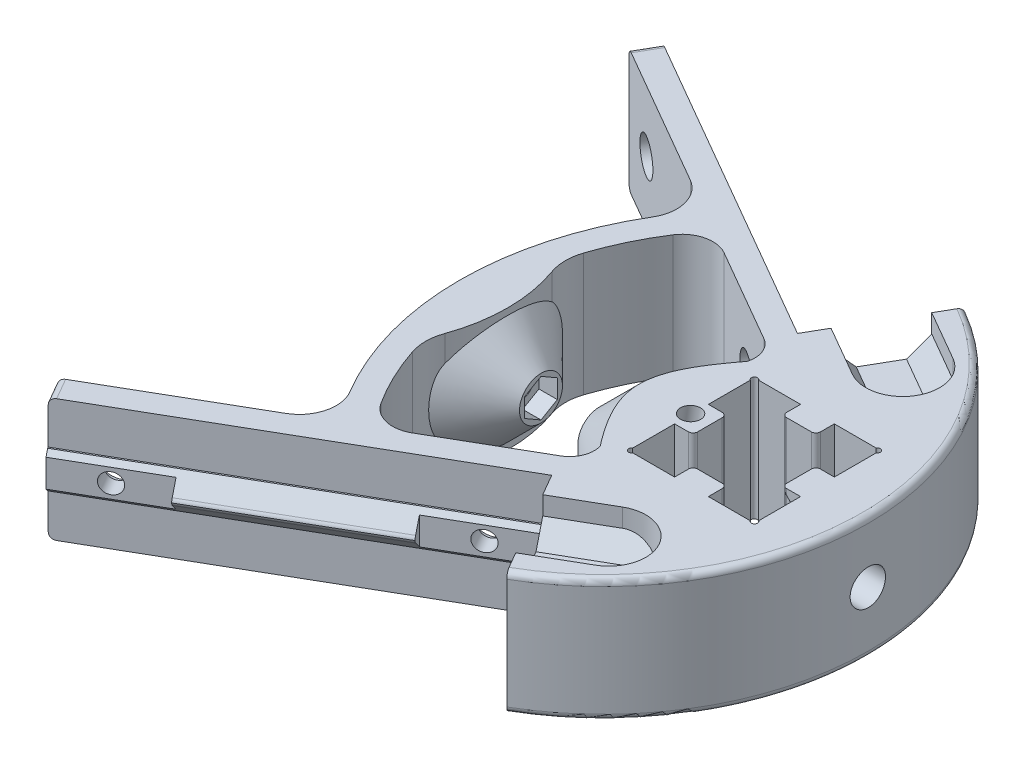
SolidWorks part; units mm, degrees
ref_plane "Front Plane" through (0, 0, 0) normal (0, 0, 1) x (1, 0, 0)
ref_plane "Top Plane" through (0, 0, 0) normal (0, 1, 0) x (1, 0, 0)
ref_plane "Right Plane" through (0, 0, 0) normal (1, 0, 0) x (0, 0, -1)
sketch "Sketch-extrusion profile" plane through (0, 0, 0) normal (0, 1, 0) x (1, 0, 0)
  line L0 (0, 7) -> (0, 0) construction
  line L1 (0, 7) -> (-2, 7) construction
  line L2 (-3, 8) -> (-3, 10) construction
  line L3 (-3, 10) -> (-10, 10) construction
  line L4 (0, 0) -> (-10, 10) construction
  line L5 (-7, 0) -> (-7, 2) construction
  line L6 (-8, 3) -> (-10, 3) construction
  line L7 (-10, 3) -> (-10, 10) construction
  line L8 (7, 0) -> (7, 2) construction
  line L9 (8, 3) -> (10, 3) construction
  line L10 (10, 3) -> (10, 10) construction
  line L11 (3, 10) -> (10, 10) construction
  line L12 (3, 8) -> (3, 10) construction
  line L13 (0, 7) -> (2, 7) construction
  line L14 (0, -7) -> (2, -7) construction
  line L15 (3, -8) -> (3, -10) construction
  line L16 (3, -10) -> (10, -10) construction
  line L17 (10, -3) -> (10, -10) construction
  line L18 (8, -3) -> (10, -3) construction
  line L19 (7, 0) -> (7, -2) construction
  line L20 (-7, 0) -> (-7, -2) construction
  line L21 (-8, -3) -> (-10, -3) construction
  line L22 (-10, -3) -> (-10, -10) construction
  line L23 (-3, -10) -> (-10, -10) construction
  line L24 (-3, -8) -> (-3, -10) construction
  line L25 (0, -7) -> (-2, -7) construction
  line L26 (0, 0) -> (4.0502, 0) construction
  line L27 (10.25, 2.75) -> (10.25, 9.567)
  line L28 (2.75, 10.25) -> (9.567, 10.25)
  line L29 (2.75, 8) -> (2.75, 10.25)
  line L30 (0, 7.25) -> (2, 7.25)
  line L31 (0, 7.25) -> (-2, 7.25)
  line L32 (-2.75, 8) -> (-2.75, 10.25)
  line L33 (-2.75, 10.25) -> (-9.567, 10.25)
  line L34 (-10.25, 2.75) -> (-10.25, 9.567)
  line L35 (-8, 2.75) -> (-10.25, 2.75)
  line L36 (-7.25, 0) -> (-7.25, 2)
  line L37 (-7.25, 0) -> (-7.25, -2)
  line L38 (-8, -2.75) -> (-10.25, -2.75)
  line L39 (-10.25, -2.75) -> (-10.25, -9.567)
  line L40 (-2.75, -10.25) -> (-9.567, -10.25)
  line L41 (-2.75, -8) -> (-2.75, -10.25)
  line L42 (0, -7.25) -> (-2, -7.25)
  line L43 (0, -7.25) -> (2, -7.25)
  line L44 (2.75, -8) -> (2.75, -10.25)
  line L45 (2.75, -10.25) -> (9.567, -10.25)
  line L46 (10.25, -2.75) -> (10.25, -9.567)
  line L47 (8, -2.75) -> (10.25, -2.75)
  line L48 (7.25, 0) -> (7.25, -2)
  line L49 (7.25, 0) -> (7.25, 2)
  line L50 (8, 2.75) -> (10.25, 2.75)
  line L51 (-10.25, 2.75) -> (-10.25, 10.25) construction
  line L52 (-2.75, 10.25) -> (-10.25, 10.25) construction
  line L53 (-10.25, -2.75) -> (-10.25, -10.25) construction
  line L54 (-2.75, -10.25) -> (-10.25, -10.25) construction
  line L55 (2.75, -10.25) -> (10.25, -10.25) construction
  line L56 (10.25, -2.75) -> (10.25, -10.25) construction
  line L57 (2.75, 10.25) -> (10.25, 10.25) construction
  line L58 (10.25, 2.75) -> (10.25, 10.25) construction
  arc A0 (-7, 2) -> (-8, 3) centre (-8, 2) ccw construction
  arc A1 (-7, -2) -> (-8, -3) centre (-8, -2) cw construction
  arc A2 (-3, -8) -> (-2, -7) centre (-2, -8) cw construction
  arc A3 (2, -7) -> (3, -8) centre (2, -8) cw construction
  arc A4 (8, -3) -> (7, -2) centre (8, -2) cw construction
  arc A5 (7, 2) -> (8, 3) centre (8, 2) cw construction
  arc A6 (3, 8) -> (2, 7) centre (2, 8) cw construction
  arc A7 (-2, 7) -> (-3, 8) centre (-2, 8) cw construction
  arc A8 (2.75, 8) -> (2, 7.25) centre (2, 8) cw
  arc A9 (-2, 7.25) -> (-2.75, 8) centre (-2, 8) cw
  arc A10 (-7.25, 2) -> (-8, 2.75) centre (-8, 2) ccw
  arc A11 (-7.25, -2) -> (-8, -2.75) centre (-8, -2) cw
  arc A12 (-2.75, -8) -> (-2, -7.25) centre (-2, -8) cw
  arc A13 (2, -7.25) -> (2.75, -8) centre (2, -8) cw
  arc A14 (8, -2.75) -> (7.25, -2) centre (8, -2) cw
  arc A15 (7.25, 2) -> (8, 2.75) centre (8, 2) cw
  arc A16 (-10.25, 9.567) -> (-9.567, 10.25) centre (-10, 10) cw
  arc A17 (-10.25, -9.567) -> (-9.567, -10.25) centre (-10, -10) ccw
  arc A18 (9.567, -10.25) -> (10.25, -9.567) centre (10, -10) ccw
  arc A19 (9.567, 10.25) -> (10.25, 9.567) centre (10, 10) cw
  point P10 (-7, 3)
  point P31 (0, 0)
  point P44 (-3, 7)
  dimension "D6" = 1
  dimension "D7" = 0.25
  dimension "D8" = 0.5
  dimension "D1" = 7
  dimension "D2" = 7
  dimension "D3" = 3
  dimension "D4" = 3
  dimension "D5" = 4
sketch "Sketch-main" plane through (0, 0, 0) normal (0, 1, 0) x (1, 0, 0)
  line L0 (-7, 0) -> (7, 0) construction
  line L1 (0, 7) -> (0, -7) construction
  line L2 (-13, 20) -> (-64.9615, 50)
  line L3 (-13, 20) -> (-3, 37.3205)
  line L4 (-64.9615, 50) -> (-66.9615, 46.5359)
  line L6 (-13, 20) -> (-24.547, 0) construction
  line L8 (3.9461, 0) -> (-11.0539, 0) construction
  line L9 (-11.0539, -14.2576) -> (-11.0539, 14.2576) construction
  line L14 (-13, -20) -> (-3, -37.3205)
  line L15 (-13, -20) -> (-64.9615, -50)
  line L16 (-64.9615, -50) -> (-66.9615, -46.5359)
  line L30 (-66.9615, 46.5359) -> (-15.004, 16.5382)
  line L31 (-66.9615, -46.5359) -> (-15.004, -16.5382)
  arc A0 (-3, 37.3205) -> (-3, -37.3205) centre (-24.547, 0) cw
  arc A1 (-13.6106, 10.9564) -> (-13.6106, -10.9564) centre (3.9461, 0) ccw
  arc A2 (-13.6106, -10.9564) -> (-15.004, -16.5382) centre (-17.004, -13.0741) cw
  arc A3 (-15.004, 16.5382) -> (-13.6106, 10.9564) centre (-17.004, 13.0741) cw
  dimension "D7" = 15
  dimension "D8" = 4
  dimension "D1" = 20
  dimension "D2" = 13
  dimension "D3" = 20
  dimension "D4" = 30
  dimension "D5" = 60
  dimension "D6" = 4
extrude "Boss-Extrude1" add sketch "Sketch-main" along normal blind 10 and the other way blind 10
extrude "Cut-Extrude1" cut sketch "Sketch-extrusion profile" against normal through all both and the other way through all
sketch "Sketch1" plane through (-18.4103, 0, -10.6292) normal (-0.866, 0, -0.5) x (-0.5, 0, 0.866)
  line L0 (-30.8205, 0) -> (-10.8205, 0) construction
  line L1 (-30.8205, -10) -> (-30.8205, 10) construction
  line L2 (-10.8205, -10) -> (-10.8205, 10) construction
  line L3 (-20.8205, 10) -> (-20.8205, 0) construction
  line L4 (-30.8205, 10) -> (-10.8205, 10) construction
  line L5 (-17.8205, 4) -> (-23.8205, 4)
  line L6 (-23.8205, 4) -> (-26.8205, 7)
  line L7 (-26.8205, 7) -> (-26.8205, 10)
  line L8 (-26.8205, 10) -> (-14.8205, 10)
  line L9 (-17.8205, 4) -> (-14.8205, 7)
  line L10 (-14.8205, 7) -> (-14.8205, 10)
  line L11 (-23.8205, -4) -> (-26.8205, -7)
  line L12 (-17.8205, -4) -> (-23.8205, -4)
  line L13 (-17.8205, -4) -> (-14.8205, -7)
  line L14 (-14.8205, -7) -> (-14.8205, -10)
  line L15 (-26.8205, -10) -> (-14.8205, -10)
  line L16 (-26.8205, -7) -> (-26.8205, -10)
  point P15 (-20.8205, 4)
  dimension "D1" = 6
  dimension "D2" = 3
  dimension "D3" = 6
  dimension "D4" = 12
extrude "Cut-Extrude2" cut sketch "Sketch1" against normal blind 15.5
mirror "Mirror1" about plane through (0, 0, 0) normal (0, 0, 1) of "Cut-Extrude2"
fillet "Fillet1" radius 6 8 edges at (2.4234, -8.5, 15.7141) (8.4234, -8.5, 26.1064) (2.4234, 8.5, 15.7141) (8.4234, 8.5, 26.1064) (2.4234, -8.5, -15.7141) (8.4234, -8.5, -26.1064) (8.4234, 8.5, -26.1064) (2.4234, 8.5, -15.7141)
sketch "Sketch3" plane through (5.4103, 0, -9.3708) normal (0.5, 0, -0.866) x (-0.866, 0, -0.5)
  line L0 (21.2583, 0) -> (81.2583, 0) construction
  line L1 (21.2583, -10) -> (21.2583, 10) construction
  line L2 (81.2583, -10) -> (81.2583, 10) construction
  line L3 (21.2583, -10) -> (81.2583, -10) construction
  line L5 (21.2583, -3) -> (81.2583, -3)
  line L6 (21.2583, -3) -> (21.2583, 3)
  line L7 (21.2583, 3) -> (81.2583, 3)
  line L8 (81.2583, -3) -> (81.2583, 3)
  line L9 (21.2583, -3) -> (81.2583, 3) construction
  line L10 (21.2583, 3) -> (81.2583, -3) construction
  point P8 (51.2583, 0)
  dimension "D1" = 10
  dimension "D2" = 6
extrude "Boss-Extrude2" add sketch "Sketch3" along normal blind 3
sketch "Sketch7" plane through (6.9103, 0, -11.9689) normal (0.5, 0, -0.866) x (-0.866, 0, -0.5)
  line L0 (51.2583, 3) -> (51.2583, -3) construction
  line L1 (81.2583, 3) -> (21.2583, 3) construction
  line L2 (21.2583, -3) -> (81.2583, -3) construction
  line L3 (21.2583, -3) -> (81.2583, -3) construction
  line L4 (21.2583, 3) -> (36.7583, 3)
  line L5 (21.2583, 3) -> (21.2583, -3)
  line L6 (21.2583, -3) -> (36.7583, -3)
  line L7 (36.7583, 3) -> (36.7583, -3)
  line L8 (81.2583, -3) -> (65.7583, -3)
  line L9 (65.7583, 3) -> (65.7583, -3)
  line L10 (81.2583, 3) -> (65.7583, 3)
  line L11 (81.2583, 3) -> (81.2583, -3)
  dimension "D1" = 15.5
extrude "Cut-Extrude6" cut sketch "Sketch7" against normal blind 2
sketch "Sketch34" plane through (-70.3718, 0, -40.6292) normal (-0.866, 0, -0.5) x (-0.5, 0, 0.866)
  line L0 (-11.0705, 3) -> (-13.8205, 0.25)
  line L1 (-11.8205, 3) -> (-10.8205, 3) construction
  line L2 (-13.8205, 3) -> (-13.8205, -3) construction
  line L3 (-10.8205, 3) -> (-10.8205, 10) construction
  line L4 (-11.8205, 0) -> (-13.8205, 0) construction
  line L5 (-11.8205, -3) -> (-11.8205, 3) construction
  line L6 (-13.8205, 0.25) -> (-13.8205, 3)
  line L7 (-13.8205, 3) -> (-11.0705, 3)
  line L9 (-13.8205, -3) -> (-11.0705, -3)
  line L10 (-13.8205, -0.25) -> (-13.8205, -3)
  line L11 (-11.0705, -3) -> (-13.8205, -0.25)
  dimension "D1" = 0.25
  dimension "D2" = 45
extrude "Cut-Extrude25" cut sketch "Sketch34" against normal blind 60
sketch "Sketch8" plane through (3.4103, 0, -5.9067) normal (-0.5, 0, 0.866) x (0.866, 0, 0.5)
  line L0 (-73.5083, 3) -> (-73.5083, -3) construction
  line L1 (-81.2583, 3) -> (-65.7583, 3) construction
  line L2 (-81.2583, -3) -> (-65.7583, -3) construction
  line L3 (-51.2583, 0) -> (-51.2583, 10) construction
  line L4 (-51.2583, 3) -> (-51.2583, -3) construction
  line L5 (-81.2583, 10) -> (-21.263, 10) construction
  circle A0 centre (-73.5083, 0) radius 1.625
  circle A1 centre (-29.0083, 0) radius 1.625
  dimension "D1" = 3.25
extrude "Cut-Extrude7" cut sketch "Sketch8" against normal through all
sketch "Sketch9" plane through (3.4103, 0, -5.9067) normal (-0.5, 0, 0.866) x (0.866, 0, 0.5)
  circle A0 centre (-73.5083, 0) radius 2.875
  circle A1 centre (-29.0083, 0) radius 2.875
  dimension "D1" = 5.75
extrude "Cut-Extrude8" cut sketch "Sketch9" against normal blind 2
fillet "Fillet3" radius 1 2 edges at (-37.4808, -0.25, -37.5981) (-37.4808, 0.25, -37.5981)
mirror "Mirror4" about plane through (0, 0, 0) normal (0, 0, 1) of "Fillet3", "Cut-Extrude25", "Cut-Extrude8", "Cut-Extrude7", "Cut-Extrude6", "Boss-Extrude2"
sketch "Sketch10" plane through (7.25, 0, 0) normal (-1, 0, 0) x (0, 0, 1)
  line L0 (0, 10) -> (0, -10) construction
  line L1 (2, 10) -> (-2, 10) construction
  line L2 (2, -10) -> (-2, -10) construction
  circle A0 centre (0, 0) radius 1.625
  dimension "D2" = 3.25
  dimension "D1" = 10
extrude "Cut-Extrude9" cut sketch "Sketch10" against normal through all
sketch "Sketch11" plane through (7.25, 0, 0) normal (-1, 0, 0) x (0, 0, 1)
  line L0 (-2.75, -10) -> (-2.75, 10) construction
  line L1 (2.75, -7.75) -> (-2.75, -7.75)
  line L2 (2.75, -7.75) -> (2.75, 7.75)
  line L3 (2.75, 7.75) -> (-2.75, 7.75)
  line L4 (-2.75, -7.75) -> (-2.75, 7.75)
  line L5 (2.75, -7.75) -> (-2.75, 7.75) construction
  line L6 (2.75, 7.75) -> (-2.75, -7.75) construction
  point P0 (0, 0)
  dimension "D1" = 15.5
extrude "Cut-Extrude11" cut sketch "Sketch11" against normal blind 2
ref_plane "Plane1" through (18.547, 10, 0) normal (1, 0, 0) x (0, 0, -1)
sketch "Sketch13" plane through (18.547, 10, 0) normal (1, 0, 0) x (0, 0, -1)
  circle A0 centre (0, -10) radius 2.875
  dimension "D1" = 5.75
extrude "Cut-Extrude12" cut sketch "Sketch13" against normal offset from surface (6.297 mm away) 2 up to face at (10.25, 0, 6.1585)
sketch "Sketch27" plane through (0, 0, 2.75) normal (0, 0, 1) x (1, 0, 0)
  line L0 (9.25, 7.75) -> (8, 7.75) construction
  line L1 (7.25, 7.75) -> (8, 7.75) construction
  line L2 (9.25, -7.75) -> (8, -7.75) construction
  line L3 (8, -7.75) -> (7.25, -7.75) construction
  line L4 (9.25, 7.75) -> (8, 7.75)
  line L5 (7.25, 7.75) -> (8, 7.75)
  line L6 (9.25, -7.75) -> (8, -7.75)
  line L7 (8, -7.75) -> (7.25, -7.75)
  line L8 (7.25, -7.75) -> (7.25, -9.75)
  line L9 (7.25, -9.75) -> (9.25, -7.75)
  line L10 (7.25, 7.75) -> (7.25, 9.75)
  line L11 (7.25, 9.75) -> (9.25, 7.75)
  dimension "D1" = 45
  dimension "D2" = 45
extrude "Cut-Extrude19" cut sketch "Sketch27" against normal up to next
mirror "Mirror5" [suppressed] about plane through (0, 0, 0) normal (0, 1, 0)
fillet "Fillet8" radius 1 6 edges at (18.547, -10, 0) (18.547, 10, 0) (-65.9615, -10, 48.2679) (-65.9615, 10, 48.2679) (-65.9615, -10, -48.2679) (-65.9615, 10, -48.2679)
sketch "Sketch14" [suppressed] plane through (0, 0, 0) normal (0, 1, 0) x (1, 0, 0)
  line L0 (-11.75, 22.1651) -> (-2.75, 16.9689)
  line L1 (-2.75, 16.9689) -> (-2.75, 7.25)
  line L2 (-2.75, 8) -> (-2.75, 10.25) construction
  line L3 (2, 7.25) -> (-2, 7.25) construction
  line L4 (2.75, 10.25) -> (2.75, 8) construction
  line L5 (3.2272, 29.1064) -> (-5, 33.8564) construction
  line L6 (-11.75, 22.1651) -> (-4.25, 35.1554)
  line L7 (-11, 23.4641) -> (-13, 20) construction
  line L8 (-3.5, 36.4545) -> (-5, 33.8564) construction
  line L9 (-4.25, 35.1554) -> (2.75, 31.114)
  line L10 (2.75, 31.114) -> (2.75, 7.25)
  line L11 (2.75, 7.25) -> (-2.75, 7.25)
  line L12 (-2.7728, 18.7141) -> (-11, 23.4641) construction
  line L13 (0, 0) -> (-39.9382, 0) construction
  line L14 (-2.75, -16.9689) -> (-2.75, -7.25)
  line L15 (2.75, -7.25) -> (-2.75, -7.25)
  line L16 (2.75, -31.114) -> (2.75, -7.25)
  line L17 (-4.25, -35.1554) -> (2.75, -31.114)
  line L18 (-11.75, -22.1651) -> (-2.75, -16.9689)
  line L19 (-11.75, -22.1651) -> (-4.25, -35.1554)
  dimension "D1" = 1.5
  dimension "D2" = 1.5
extrude "Cut-Extrude13" [suppressed] cut sketch "Sketch14" against normal offset from surface 4 and the other way offset from surface 4 up to face at (-0.156, -4, -24.1315) other way up to face at (-0.156, 4, -24.1315)
sketch "Sketch28" [suppressed] plane through (2.75, 0, 0) normal (1, 0, 0) x (0, 0, -1)
  line L0 (7.25, 10) -> (10.25, 10)
  line L1 (7.25, 10) -> (8, 10) construction
  line L2 (10.25, 10) -> (8, 10) construction
  line L3 (10.25, -20) -> (10.25, 20) construction
  line L4 (10.25, 10) -> (7.25, 13)
  line L5 (7.25, 10) -> (7.25, 20) construction
  line L6 (7.25, 13) -> (7.25, 10)
  line L7 (5.3832, 0) -> (-4.7577, 0) construction
  line L8 (0, 2.994) -> (0, -3.4826) construction
  line L9 (-7.25, 10) -> (-10.25, 10)
  line L10 (-10.25, 10) -> (-7.25, 13)
  line L11 (-7.25, 13) -> (-7.25, 10)
  line L12 (7.25, -10) -> (10.25, -10)
  line L13 (10.25, -10) -> (7.25, -13)
  line L14 (7.25, -13) -> (7.25, -10)
  line L15 (-7.25, -13) -> (-7.25, -10)
  line L16 (-7.25, -10) -> (-10.25, -10)
  line L17 (-10.25, -10) -> (-7.25, -13)
  dimension "D1" = 45
extrude "Cut-Extrude20" [suppressed] cut sketch "Sketch28" against normal up to next
fillet "Fillet6" [suppressed] radius 5
sketch "Sketch18" [suppressed] plane through (18.547, 20, 0) normal (1, 0, 0) x (0, 0, -1)
  line L0 (-37.3205, -22.142) -> (37.3205, -22.142) construction
  line L1 (-37.3205, -39) -> (-37.3205, -1) construction
  line L2 (37.3205, -39) -> (37.3205, -1) construction
  line L3 (40.0914, -28.3306) -> (-3.7181, -28.3306) construction
  text T0 "KosseL" font "Jefferies" height 8
  text T1 "minimax" font "Trebuchet MS" height 4.5
wrap "Wrap1" [suppressed] sketch "Sketch18" source sketch "Sketch18" thickness 0.25 parameters "D1"=0.25
sketch "Sketch29" [suppressed] plane through (0, 0, 0) normal (0, 1, 0) x (1, 0, 0)
  line L0 (-45, 25.1962) -> (-45, -25.1962)
  line L1 (-66.0955, 46.0359) -> (-15.004, 16.5382) construction
  line L2 (-15.004, -16.5382) -> (-66.0955, -46.0359) construction
  line L3 (-49, 27.5056) -> (-49, -27.5056)
  line L4 (0, 5.0299) -> (0, -2.8868) construction
  line L5 (-3.4206, 0) -> (3.3651, 0) construction
  line L6 (-56.5, 40.4959) -> (-53.5973, 38.8201)
  line L7 (-53.5973, 38.8201) -> (-51.5973, 42.2842)
  line L8 (-13, 20) -> (-64.0955, 49.5) construction
  line L9 (-51.5973, 42.2842) -> (-26.4641, 27.7735)
  line L11 (-26.4641, 27.7735) -> (-28.4641, 24.3094)
  line L12 (-28.4641, 24.3094) -> (-37.5, 29.5263)
  line L13 (-28.4641, -24.3094) -> (-37.5, -29.5263)
  line L14 (-26.4641, -27.7735) -> (-28.4641, -24.3094)
  line L15 (-51.5973, -42.2842) -> (-26.4641, -27.7735)
  line L16 (-53.5973, -38.8201) -> (-51.5973, -42.2842)
  line L17 (-56.5, -40.4959) -> (-53.5973, -38.8201)
  arc A0 (-45, -25.1962) -> (-37.5, -29.5263) centre (-40, -25.1962) ccw
  arc A1 (-45, 25.1962) -> (-37.5, 29.5263) centre (-40, 25.1962) cw
  arc A2 (-49, -27.5056) -> (-56.5, -40.4959) centre (-64, -27.5056) cw
  arc A3 (-49, 27.5056) -> (-56.5, 40.4959) centre (-64, 27.5056) ccw
  point P27 (-45, -33.8564)
  point P30 (-45, 33.8564)
  point P33 (-49, -36.1658)
  point P36 (-49, 36.1658)
  dimension "D3" = 5
  dimension "D4" = 15
  dimension "D1" = 4
  dimension "D2" = 45
extrude "Boss-Extrude6" [suppressed] add sketch "Sketch29" along normal up to surface and the other way up to surface up to face at (0, 10, 0) other way up to face at (0, -10, 0)
sketch "Sketch30" [suppressed] plane through (-45, 0, 0) normal (1, 0, 0) x (0, 0, -1)
  line L0 (0, 20) -> (0, -20) construction
  line L1 (25.1962, 20) -> (-25.1962, 20) construction
  line L2 (-25.1962, -20) -> (25.1962, -20) construction
  line L3 (0, 0) -> (9.6965, 0) construction
  circle A0 centre (0, 0) radius 15
  circle A1 centre (-15.495, 15.495) radius 1.625
  circle A2 centre (15.495, 15.495) radius 1.625
  circle A3 centre (15.495, -15.495) radius 1.625
  circle A4 centre (-15.495, -15.495) radius 1.625
  dimension "D1" = 30
  dimension "D2" = 3.25
  dimension "D3" = 30.99
  dimension "D4" = 30.99
extrude "Cut-Extrude21" [suppressed] cut sketch "Sketch30" against normal up to next
sketch "Sketch31" [suppressed] plane through (-45, 0, 0) normal (1, 0, 0) x (0, 0, -1)
  circle A0 centre (-15.495, 15.495) radius 2.875
  circle A1 centre (15.495, 15.495) radius 2.875
  circle A2 centre (15.495, -15.495) radius 2.875
  circle A3 centre (-15.495, -15.495) radius 2.875
  dimension "D1" = 5.75
extrude "Cut-Extrude22" [suppressed] cut sketch "Sketch31" against normal blind 2
sketch "Sketch20" plane through (0, 0, 0) normal (0, 1, 0) x (1, 0, 0)
  line L0 (-41.0539, 31.5781) -> (-41.0539, -31.5781) construction
  line L1 (-66.0955, 46.0359) -> (-15.004, 16.5382) construction
  line L2 (-15.004, -16.5382) -> (-66.0955, -46.0359) construction
  line L3 (-41.0539, 0) -> (0, 0) construction
  line L4 (-30.3372, 25.3908) -> (-24.5516, 22.0505)
  line L5 (-43.359, 32.909) -> (-47.5096, 35.3053)
  line L6 (-47.5096, 35.3053) -> (-46.1621, 37.6394)
  line L8 (-24.5516, 22.0505) -> (-23.2041, 24.3846)
  line L9 (-23.2041, 24.3846) -> (-46.1621, 37.6394)
  line L10 (-30.3372, -25.3908) -> (-24.5516, -22.0505)
  line L11 (-24.5516, -22.0505) -> (-23.2041, -24.3846)
  line L12 (-23.2041, -24.3846) -> (-46.1621, -37.6394)
  line L13 (-47.5096, -35.3053) -> (-46.1621, -37.6394)
  line L14 (-43.359, -32.909) -> (-47.5096, -35.3053)
  arc A0 (-13.6106, 10.9564) -> (-13.6106, -10.9564) centre (3.9461, 0) ccw construction
  arc A1 (-41.7472, 13.9325) -> (-37.0459, 23.7601) centre (0, 0) cw
  arc A2 (-41.209, -24.6342) -> (-41.209, 24.6342) centre (0, 0) cw
  arc A3 (-41.209, 24.6342) -> (-43.359, 32.909) centre (-46.359, 27.7128) ccw
  arc A4 (-37.0459, 23.7601) -> (-30.3372, 25.3908) centre (-32.8372, 21.0607) cw
  arc A5 (-41.6942, 8.7139) -> (-41.6942, -8.7139) centre (-66.1408, 0) cw
  arc A6 (-41.6942, 8.7139) -> (-41.7472, 13.9325) centre (-34.1586, 11.3999) cw
  arc A7 (-41.6942, -8.7139) -> (-41.7472, -13.9325) centre (-34.1586, -11.3999) ccw
  arc A8 (-41.7472, -13.9325) -> (-37.0459, -23.7601) centre (0, 0) ccw
  arc A9 (-37.0459, -23.7601) -> (-30.3372, -25.3908) centre (-32.8372, -21.0607) ccw
  arc A10 (-41.209, -24.6342) -> (-43.359, -32.909) centre (-46.359, -27.7128) cw
  point P19 (-37.7465, 29.6686)
  point P22 (-34.2436, 27.6462)
  dimension "D2" = 4
  dimension "D3" = 6
  dimension "D4" = 5
  dimension "D5" = 8
  dimension "D1" = 45
extrude "Boss-Extrude4" add sketch "Sketch20" along normal up to surface (10 mm away) and the other way up to surface (10 mm away) up to face at (0, 10, 0) other way up to face at (0, -10, 0)
sketch "Sketch21" plane through (0, 0, 0) normal (0, 1, 0) x (1, 0, 0)
  line L0 (-34.75, 0) -> (-25.25, 0) construction
  line L1 (-34.75, 0) -> (-34.75, 3.5)
  line L2 (-30, 0) -> (-30, 13.3519) construction
  line L3 (-25.25, 0) -> (-25.25, 3.5)
  line L4 (-34.75, 0) -> (-42.1425, 0)
  line L5 (-42.1425, 0) -> (-42.1425, 10.8925)
  line L6 (-42.1425, 10.8925) -> (-34.75, 3.5)
  line L7 (-25.25, 0) -> (-12.0832, 0)
  line L8 (-25.25, 3.5) -> (-12.0832, 16.6668)
  line L9 (-12.0832, 16.6668) -> (-12.0832, 0)
  line L10 (-44.1299, 10) -> (-9.3668, 10) construction
  line L11 (-44.1299, -10) -> (-9.3668, -10) construction
  line L12 (0, -3.6374) -> (0, 0) construction
  arc A0 (-41.7472, 13.9325) -> (-41.6942, 8.7139) centre (-34.1586, 11.3999) ccw construction
  dimension "D1" = 9.5
  dimension "D2" = 7
  dimension "D3" = 20
  dimension "D4" = 30
  dimension "D5" = 45
  dimension "D6" = 45
revolve "Revolve1" add sketch "Sketch21" angle 360 about L0
sketch "Sketch22" plane through (-34.75, 0, 0) normal (1, 0, 0) x (0, 0, -1)
  circle A0 centre (0, 0) radius 1.625
  circle A2 centre (0, 0) radius 3.5 construction
  dimension "D1" = 3.25
extrude "Cut-Extrude16" cut sketch "Sketch22" against normal through all and the other way blind 20
sketch "Sketch23" plane through (-34.75, 0, 0) normal (1, 0, 0) x (0, 0, -1)
  line L0 (0, 3.075) -> (0, 0) construction
  line L1 (0, 3.075) -> (-2.663, 1.5375)
  line L2 (-2.663, 1.5375) -> (-2.663, -1.5375)
  line L3 (-2.663, -1.5375) -> (0, -3.075)
  line L4 (0, -3.075) -> (2.663, -1.5375)
  line L5 (2.663, -1.5375) -> (2.663, 1.5375)
  line L6 (2.663, 1.5375) -> (0, 3.075)
  circle A0 centre (0, 0) radius 2.663 construction
  circle A1 centre (0, 0) radius 1.625 construction
  dimension "D1" = 6.15
extrude "Cut-Extrude17" cut sketch "Sketch23" against normal blind 3
sketch "Sketch32" plane through (-12.0832, 0, 0) normal (1, 0, 0) x (0, 0, -1)
  line L0 (-13.3334, 10) -> (13.3334, 10) construction
  line L1 (13.3334, -10) -> (-13.3334, -10) construction
  line L2 (-13.3334, 10) -> (13.3334, 10)
  line L3 (13.3334, -10) -> (-13.3334, -10)
  arc A0 (13.3334, 10) -> (-13.3334, 10) centre (0, 0) ccw construction
  arc A1 (-13.3334, -10) -> (13.3334, -10) centre (0, 0) ccw construction
  arc A2 (13.3334, 10) -> (-13.3334, 10) centre (0, 0) ccw
  arc A3 (-13.3334, -10) -> (13.3334, -10) centre (0, 0) ccw
extrude "Cut-Extrude23" cut sketch "Sketch32" against normal through all
ref_plane "Plane2" through (-48.0107, 10, 0) normal (-1, 0, 0) x (0, 0, 1)
sketch "Sketch24" plane through (-48.0107, 10, 0) normal (-1, 0, 0) x (0, 0, 1)
  circle A0 centre (0, -10) radius 2.875
  dimension "D1" = 5.75
extrude "Cut-Extrude18" cut sketch "Sketch24" against normal offset from surface (8.2607 mm away) 2 up to face at (-37.75, 0, -1.625)
sketch "Sketch25" plane through (0, 0, 0) normal (0, 0, 1) x (1, 0, 0)
  line L0 (0, 0) -> (-24.9124, 0) construction
  line L1 (-9.8566, 13.7284) -> (-13.6726, -12.6025) construction
  line L2 (-10.0521, 12.3798) -> (-11.6603, 12.6129)
  line L3 (-11.6603, 12.6129) -> (-13.7691, -1.9384)
  line L4 (-13.7691, -1.9384) -> (-15.3773, -1.7053)
  line L5 (-15.3773, -1.7053) -> (-17.4363, -15.9129)
  line L6 (-17.4363, -15.9129) -> (-14.2199, -16.379)
  line L7 (-14.2199, -16.379) -> (-10.0521, 12.3798)
  dimension "D1" = 3.25
  dimension "D2" = 1.625
revolve "Cut-Revolve1" cut sketch "Sketch25" angle 360 about L7
sketch "Sketch26" plane through (-0.5584, -3.8529, 0) normal (-0.1434, -0.9897, 0) x (0.9897, -0.1434, 0)
  line L0 (-8.7098, 2.75) -> (-8.7098, -2.75) construction
  line L1 (-11.7237, 3.25) -> (-14.5383, 1.625)
  line L2 (-14.5383, 1.625) -> (-14.5383, -1.625)
  line L3 (-14.5383, -1.625) -> (-11.7237, -3.25)
  line L4 (-11.7237, -3.25) -> (-8.9091, -1.625)
  line L5 (-8.9091, -1.625) -> (-8.9091, 1.625)
  line L6 (-8.9091, 1.625) -> (-11.7237, 3.25)
  circle A0 centre (-11.7237, 0) radius 3.5
  circle A1 centre (-11.7237, 0) radius 2.8146 construction
  dimension "D1" = 7
  dimension "D2" = 6.5
extrude "Boss-Extrude5" add sketch "Sketch26" along normal up to surface (7.4031 mm away) up to face at (0, -10, 0)
sketch "Sketch33" plane through (0, -10, 0) normal (0, -1, 0) x (1, 0, 0)
  line L0 (-10.25, 2.75) -> (-10.25, 9.567) construction
  line L1 (-10.25, 2.75) -> (-7.074, 2.75)
  line L2 (-10.25, 2.75) -> (-10.25, 5.9103)
  line L3 (-10.25, 5.9103) -> (-7.074, 5.9103)
  line L4 (-7.074, 2.75) -> (-7.074, 5.9103)
  line L5 (-8, 2.75) -> (-10.25, 2.75) construction
  line L7 (-10.25, -2.75) -> (-7.3329, -2.75)
  line L8 (-10.25, -2.75) -> (-10.25, -5.9385)
  line L9 (-10.25, -5.9385) -> (-7.3329, -5.9385)
  line L10 (-7.3329, -2.75) -> (-7.3329, -5.9385)
extrude "Cut-Extrude24" cut sketch "Sketch33" against normal through all
sketch "Sketch35" [suppressed] plane through (-49, 0, 0) normal (-1, 0, 0) x (0, 0, 1)
  line L0 (-15.495, 15.495) -> (-15.495, -15.495)
ref_plane "Plane3" [suppressed] through (0, 0, -15.495) normal (0, 0, 1) x (0, -1, 0)
sketch "Sketch36" [suppressed] plane through (0, 0, -15.495) normal (0, 0, 1) x (0, -1, 0)
  line L0 (0, -49) -> (0, -10.5837) construction
  line L1 (-15.495, -49) -> (15.495, -49) construction
  line L2 (-15.495, -49) -> (-26.9339, 23.2222) construction
  line L3 (-19.1895, -25.6738) -> (-21.6587, -26.0649)
  line L4 (-21.6587, -26.0649) -> (-29.4031, 22.8311)
  line L5 (-29.4031, 22.8311) -> (-26.9339, 23.2222)
  line L6 (-19.1895, -25.6738) -> (-26.9339, 23.2222)
  dimension "D1" = 9
  dimension "D2" = 2.5
revolve "Cut-Revolve2" [suppressed] cut sketch "Sketch36" angle 360 about L2
mirror "Mirror6" [suppressed] about plane through (0, 0, 0) normal (0, 0, 1)
mirror "Mirror7" [suppressed] about plane through (0, 0, 0) normal (0, 1, 0)
sketch "assembly" plane through (0, 0, 0) normal (1, 0, 0) x (0, 0, -1)
  line L0 (0, -55.7064) -> (0, 54.0461)
equation "\"M3CapDepth\"= 2"
equation "\"M3ScrewDiameter\"= 3.25"
equation "\"M3CapDiameter\"=5.75"
equation "\"ExtrusionNutLength\"= 15.5"
equation "\"D1@Cut-Extrude2\"=\"ExtrusionNutLength\""
equation "\"ExtrusionWidth\"=6"
equation "\"D2@Sketch3\"=\"ExtrusionWidth\""
equation "\"D1@Sketch7\"=\"ExtrusionNutLength\""
equation "\"D1@Sketch8\"=\"M3ScrewDiameter\""
equation "\"D1@Sketch9\"=\"M3CapDiameter\""
equation "\"D1@Cut-Extrude8\"=\"M3CapDepth\""
equation "\"D2@Sketch10\"=\"M3ScrewDiameter\""
equation "\"D1@Sketch11\"=\"ExtrusionNutLength\""
equation "\"D1@Sketch13\"=\"M3CapDiameter\""
equation "\"VertexAccessDepth\"=45"
equation "\"D1@Sketch20\"=\"VertexAccessDepth\""
equation "\"BearingSetWidth\"=9.5"
equation "\"D1@Sketch21\"=\"BearingSetWidth\""
equation "\"D1@Sketch22\"=\"M3ScrewDiameter\""
equation "\"D1@Sketch24\"=\"M3CapDiameter\""
equation "\"D2@Sketch25\"=\"M3ScrewDiameter\"/2"
equation "\"D2@Sketch29\"=\"VertexAccessDepth\""
equation "\"D2@Sketch30\"=\"M3ScrewDiameter\""
equation "\"D1@Sketch31\"=\"M3CapDiameter\""
